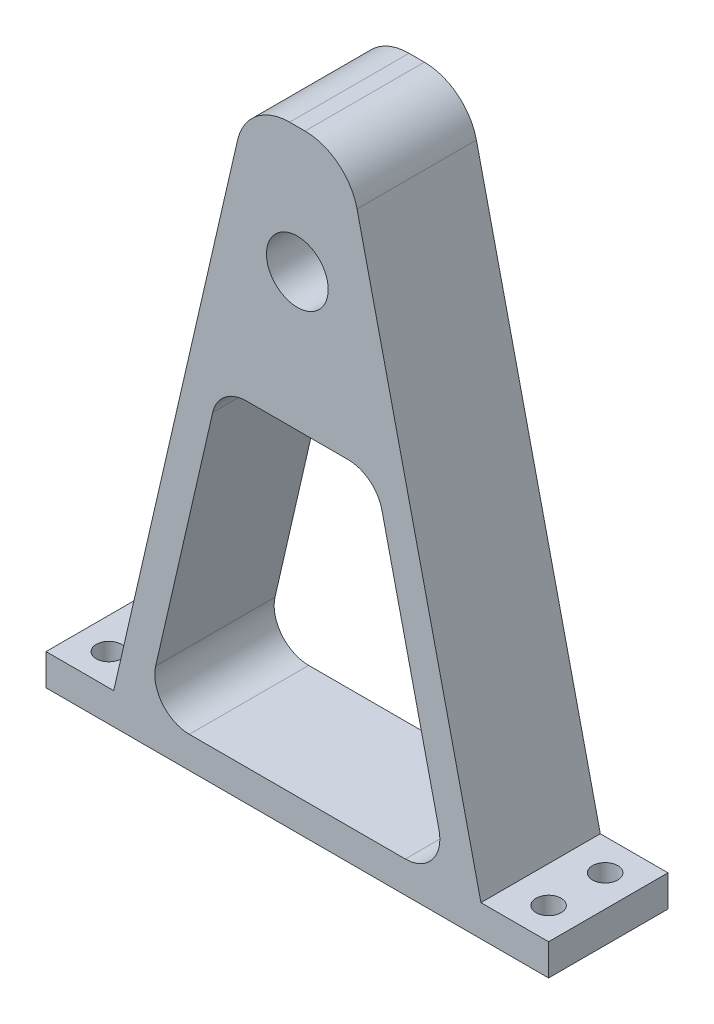
SolidWorks part; units mm, degrees
note: The reader was unsure of these and kept them because the rebuilt part matched: shared geometry of "Sketch1<3>".
ref_plane "Front Plane" through (0, 0, 0) normal (0, 0, 1) x (1, 0, 0)
ref_plane "Top Plane" through (0, 0, 0) normal (0, 1, 0) x (1, 0, 0)
ref_plane "Right Plane" through (0, 0, 0) normal (1, 0, 0) x (0, 0, -1)
sketch "Sketch1" plane through (0, 0, 0) normal (0, 0, 1) x (1, 0, 0)
  line L1 (-7.9918, 47.3647) -> (7.9918, 47.3647)
  line L3 (-30, -50) -> (30.0414, -50)
  line L5 (-40, -45) -> (40, -45)
  line L6 (-40, -45) -> (-40, -50)
  line L7 (-40, -50) -> (40, -50)
  line L8 (40, -45) -> (40, -50)
  line L14 (-7.9918, 47.3647) -> (-30, -48.3611)
  line L16 (-30, -48.3611) -> (30, -48.3611)
  line L17 (-40, -45) -> (40, -45)
  line L18 (-40, -45) -> (-40, -50)
  line L19 (-40, -50) -> (40, -50)
  line L20 (40, -45) -> (40, -50)
  line L21 (7.9918, 47.3647) -> (30, -48.3611)
  circle A0 centre (0, 27.3647) radius 4.915
  point P0 (0, 0)
  point P4 (0, 47.3647)
  point P9 (0, -45)
  dimension "D1" = 20
extrude "Boss-Extrude1" add sketch "Sketch1" along normal blind 12 and the other way blind 7
extrude "Boss-Extrude2" add sketch "Sketch1<3>" against normal blind 7 and the other way blind 12
sketch "Sketch1<3>" plane through (0, 0, 0) normal (0, 0, 1) x (1, 0, 0) same geometry as "Sketch1"
sketch "Sketch2" plane through (0, -45, 0) normal (0, 1, 0) x (1, 0, 0)
  line L0 (-40, 7) -> (-29.2273, 7) construction
  line L1 (-40, -12) -> (-40, 7) construction
  line L2 (-40, -12) -> (-29.2273, -12) construction
  line L3 (40, -12) -> (40, 7) construction
  circle A0 centre (-35, 2) radius 2
  circle A4 centre (-35, -7) radius 2
  circle A5 centre (35, 2) radius 2
  circle A6 centre (35, -7) radius 2
  dimension "D1" = 5
  dimension "D2" = 5
  dimension "D6" = 5
  dimension "D8" = 5
  dimension "D3" = 5
  dimension "D4" = 5
  dimension "D5" = 5
  dimension "D7" = 5
extrude "Cut-Extrude1" cut sketch "Sketch2" against normal up to next
sketch "Sketch3" plane through (0, 0, 0) normal (0, 0, 1) x (1, 0, 0)
  line L0 (-12.4866, 5.4994) -> (12.4866, 5.4994)
  line L1 (-12.4866, 5.4994) -> (-24.0968, -45)
  line L2 (12.4866, 5.4994) -> (24.0968, -45)
  line L3 (-24.0968, -45) -> (24.0968, -45)
  line L4 (-7.9918, 47.3647) -> (7.9918, 47.3647) construction
  line L5 (-7.9918, 47.3647) -> (-29.2273, -45) construction
  line L6 (7.9918, 47.3647) -> (29.2273, -45) construction
  line L8 (29.2273, -45) -> (40, -45) construction
  dimension "D1" = 5
  dimension "D2" = 5
extrude "Cut-Extrude2" cut sketch "Sketch3" against normal up to next and the other way up to next
fillet "Fillet3" radius 8.5 2 edges at (-7.9918, 47.3647, 2.5) (7.9918, 47.3647, 2.5)
fillet "Fillet4" radius 5.5 4 edges at (24.0968, -45, 2.5) (-24.0968, -45, 2.5) (-12.4866, 5.4994, 2.5) (12.4866, 5.4994, 2.5)
